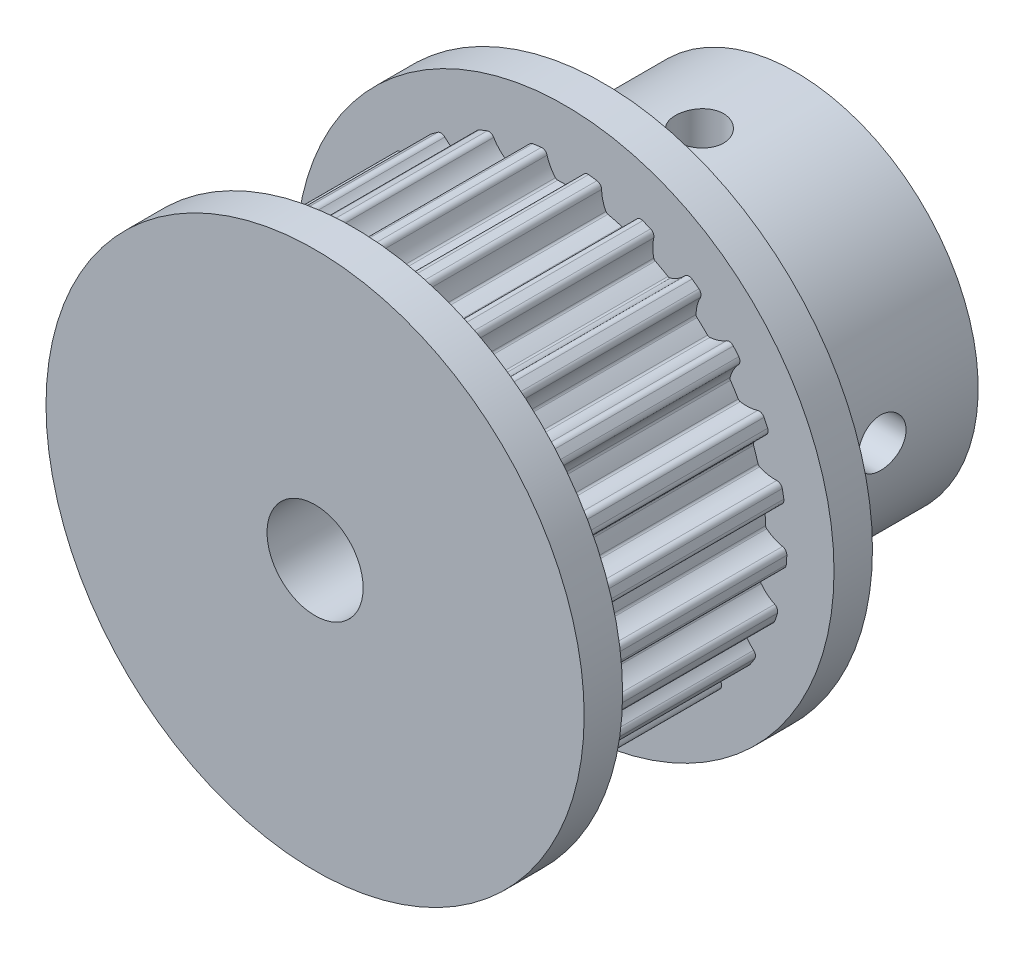
SolidWorks part; units mm, degrees
material "6061-T6 (SS)"
ref_plane "前基準面" through (0, 0, 0) normal (0, 0, 1) x (1, 0, 0)
ref_plane "上基準面" through (0, 0, 0) normal (0, 1, 0) x (1, 0, 0)
ref_plane "右基準面" through (0, 0, 0) normal (1, 0, 0) x (0, 0, -1)
sketch "草圖1" plane through (0, 0, 0) normal (0, 0, 1) x (1, 0, 0)
  circle A0 centre (0, 0) radius 11.555
  dimension "D1" = 23.11
extrude "填料-伸長1" add sketch "草圖1" along normal mid plane 11
sketch "草圖2" plane through (0, 0, 5.5) normal (0, 0, 1) x (1, 0, 0)
  line L0 (0, 0) -> (0, 11.809) construction
  line L1 (-0.975, 11.809) -> (0.975, 11.809) construction
  arc A0 (-0.3761, 10.4382) -> (0.3761, 10.4382) centre (0, 0) cw
  circle A1 centre (0, 0) radius 11.555 construction
  arc A2 (-1.2291, 11.4894) -> (-0.9293, 11.2853) centre (-1.1993, 11.211) cw
  arc A3 (-0.9293, 11.2853) -> (-0.493, 10.4878) centre (0.975, 11.809) ccw
  arc A4 (-0.493, 10.4878) -> (-0.3761, 10.4382) centre (-0.3815, 10.5881) ccw
  arc A5 (0.493, 10.4878) -> (0.3761, 10.4382) centre (0.3815, 10.5881) cw
  arc A6 (0.9293, 11.2853) -> (0.493, 10.4878) centre (-0.975, 11.809) cw
  arc A7 (1.2291, 11.4894) -> (0.9293, 11.2853) centre (1.1993, 11.211) ccw
  point P6 (0, 10.445)
  point P18 (0, 11.555)
  dimension "D1" = 1.11
  dimension "D2" = 0.15
  dimension "D3" = 1.975
  dimension "D4" = 0.28
  dimension "D5" = 1.95
  dimension "D6" = 0.254
extrude "除料-伸長1" cut sketch "草圖2" against normal through all and the other way through all flip side to cut
pattern_circular "環狀複製排列1" count 25 over 360 about axis through (0, 0, 5.5) along (0, 0, 1) of "除料-伸長1"
sketch "草圖3" plane through (0, 0, 5.5) normal (0, 0, 1) x (1, 0, 0)
  circle A0 centre (0, 0) radius 14
  dimension "D1" = 28
extrude "填料-伸長2" add sketch "草圖3" along normal blind 2
mirror "鏡射1" about plane through (0, 0, 0) normal (0, 0, 1) of "填料-伸長2"
sketch "草圖5" plane through (0, 0, -7.5) normal (0, 0, -1) x (-1, 0, 0)
  circle A0 centre (0, 0) radius 9.5
  dimension "D1" = 19
extrude "填料-伸長3" add sketch "草圖5" along normal blind 10
sketch "草圖4" plane through (0, 0, 7.5) normal (0, 0, 1) x (1, 0, 0)
  circle A0 centre (0, 0) radius 2.5
  dimension "D1" = 5
extrude "除料-伸長2" cut sketch "草圖4" against normal through all
hole_wizard "M3x0.5 螺紋孔1" positions "草圖6" profile "草圖7" tap size "M3x0.5" standard "Ansi Metric" end condition through all
sketch "草圖6" plane through (0, 0, 0) normal (0, 1, 0) x (1, 0, 0)
  point P0 (0, 12.5)
  point P26 (0, 0)
sketch "草圖7" plane through (0, 0, -12.5) normal (1, 0, 0) x (0, 0, -1)
  line L0 (0, 0) -> (0, 14)
  line L1 (0, 14) -> (1.25, 14)
  line L2 (1.25, 14) -> (1.25, 0)
  line L5 (1.25, 0) -> (0, 0)
  line L11 (0, -6.35) -> (0, 107.95) construction
  dimension "貫穿螺孔鑽直徑" = 2.5
  dimension "貫穿螺孔鑽深度" = 14
pattern_circular "環狀複製排列2" count 2 every 90 about axis through (0, 0, -17.5) along (0, 0, -1) of "M3x0.5 螺紋孔1"
